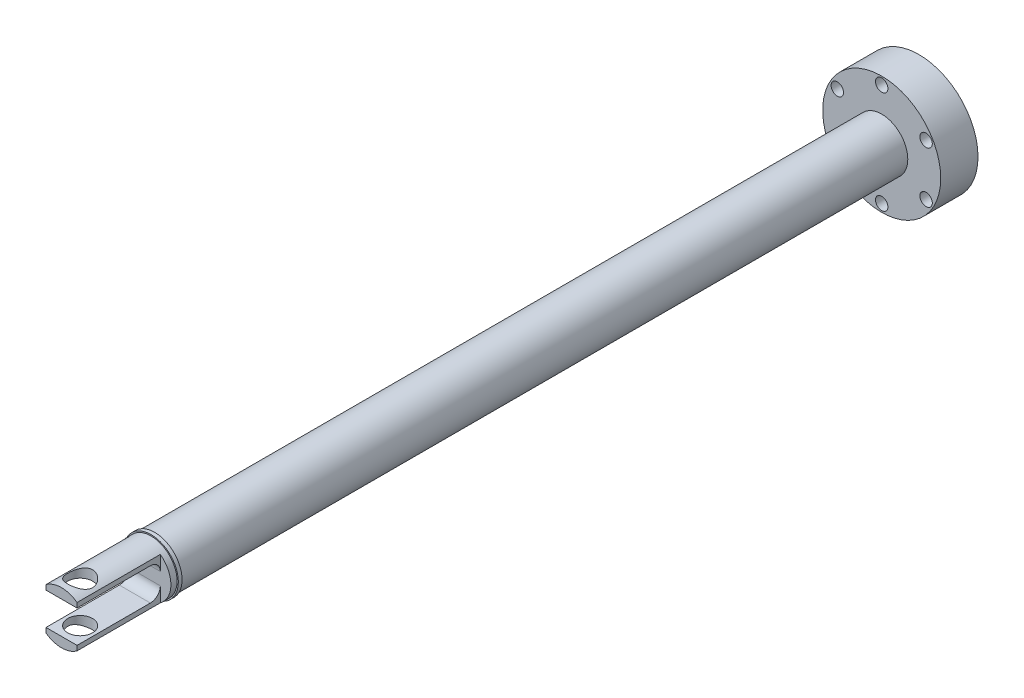
SolidWorks part; units mm, degrees
ref_plane "Płaszczyzna przednia" through (0, 0, 0) normal (0, 0, 1) x (1, 0, 0)
ref_plane "Płaszczyzna górna" through (0, 0, 0) normal (0, 1, 0) x (1, 0, 0)
ref_plane "Płaszczyzna prawa" through (0, 0, 0) normal (1, 0, 0) x (0, 0, -1)
sketch "Szkic1" plane through (0, 0, 0) normal (0, 0, 1) x (1, 0, 0)
  circle A0 centre (0, 0) radius 47.5
  dimension "D1" = 95
extrude "Dodanie-wyciągnięcie1" add sketch "Szkic1" along normal blind 30 contours A0
sketch "Szkic2" plane through (0, 0, 30) normal (0, 0, 1) x (1, 0, 0)
  circle A0 centre (0, 41.25) radius 5
  dimension "D1" = 10
  dimension "D2" = 41.25
extrude "Wytnij-wyciągnięcie1" cut sketch "Szkic2" against normal up to next
pattern_circular "Szyk kołowy1" count 6 over 360 about axis through (0, 0, 30) along (0, 0, 1) of "Wytnij-wyciągnięcie1"
sketch "Szkic3" plane through (0, 0, 30) normal (0, 0, 1) x (1, 0, 0)
  circle A0 centre (0, 0) radius 21
  dimension "D1" = 42
extrude "Dodanie-wyciągnięcie2" add sketch "Szkic3" along normal blind 585
sketch "Szkic4" plane through (0, 0, 615) normal (0, 0, 1) x (1, 0, 0)
  line L0 (-16.4924, 13) -> (16.4924, 13)
  line L1 (-16.4924, -13) -> (16.4924, -13)
  circle A1 centre (0, 0) radius 21 construction
  arc A2 (-16.4924, -13) -> (16.4924, -13) centre (0, 0) ccw
  arc A3 (16.4924, 13) -> (-16.4924, 13) centre (0, 0) ccw
  dimension "D1" = 13
  dimension "D2" = 13
extrude "Dodanie-wyciągnięcie3" add sketch "Szkic4" along normal blind 75
sketch "Szkic5" plane through (0, 0, 615) normal (0, 0, 1) x (1, 0, 0)
  circle A0 centre (0, 0) radius 22
  dimension "D1" = 44
extrude "Dodanie-wyciągnięcie4" add sketch "Szkic5" along normal blind 3
sketch "Szkic7" plane through (0, 0, 618) normal (0, 0, 1) x (1, 0, 0)
  circle A0 centre (0, 0) radius 21 construction
  circle A1 centre (0, 0) radius 21
extrude "Dodanie-wyciągnięcie5" add sketch "Szkic7" along normal blind 5
sketch "Szkic8" plane through (0, -13, 0) normal (0, 1, 0) x (1, 0, 0)
  line L0 (-16.4924, -690) -> (16.4924, -690) construction
  line L2 (16.4924, -690) -> (-16.4924, -690) construction
  circle A0 centre (0, -675) radius 10
  point P6 (0, -690)
  dimension "D1" = 20
  dimension "D2" = 15
extrude "Wytnij-wyciągnięcie2" cut sketch "Szkic8" against normal up to next and the other way through all
sketch "Szkic9" plane through (0, 0, 690) normal (0, 0, 1) x (1, 0, 0)
  line L0 (-12.4924, 13) -> (-12.4924, 16.8801)
  line L1 (-16.4924, 13) -> (16.4924, 13)
  line L2 (-16.4924, 13) -> (-12.4924, 13)
  line L3 (0, 16.8801) -> (0, 8.9496) construction
  line L4 (16.4924, 13) -> (12.4924, 13)
  line L5 (12.4924, 13) -> (12.4924, 16.8801)
  line L6 (0, 0) -> (11.8793, 0) construction
  line L7 (12.4924, -13) -> (12.4924, -16.8801)
  line L8 (16.4924, -13) -> (12.4924, -13)
  line L9 (-16.4924, -13) -> (-12.4924, -13)
  line L10 (-12.4924, -13) -> (-12.4924, -16.8801)
  arc A0 (12.4924, 16.8801) -> (16.4924, 13) centre (0, 0) cw
  arc A1 (16.4924, 13) -> (-16.4924, 13) centre (0, 0) ccw
  arc A2 (-12.4924, 16.8801) -> (-16.4924, 13) centre (0, 0) ccw
  arc A3 (12.4924, -16.8801) -> (16.4924, -13) centre (0, 0) ccw
  arc A4 (-12.4924, -16.8801) -> (-16.4924, -13) centre (0, 0) cw
  dimension "D2" = 4
  dimension "D1" = 0
extrude "Wytnij-wyciągnięcie3" cut sketch "Szkic9" against normal up to surface (67 mm away) up to face at (0, 0, 623)
fillet "Zaokrąglenie1" radius 8 2 edges at (0, -13, 623) (0, 13, 623)
